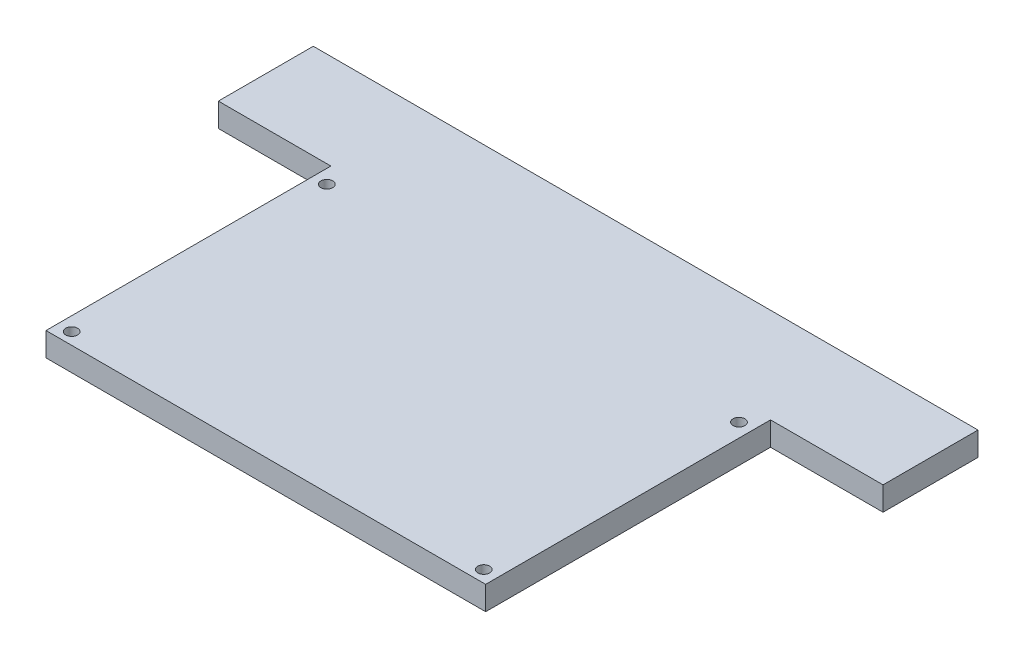
SolidWorks part; units mm, degrees
ref_plane "Front Plane" through (0, 0, 0) normal (0, 0, 1) x (1, 0, 0)
ref_plane "Top Plane" through (0, 0, 0) normal (0, 1, 0) x (1, 0, 0)
ref_plane "Right Plane" through (0, 0, 0) normal (1, 0, 0) x (0, 0, -1)
sketch "Sketch1" plane through (0, 0, 0) normal (0, 1, 0) x (1, 0, 0)
  line L0 (0, 0) -> (0, -50000) construction
  line L1 (-58.801, -38.1) -> (58.801, -38.1)
  line L2 (-58.801, -38.1) -> (-58.801, 38.1)
  line L3 (-58.801, 38.1) -> (58.801, 38.1)
  line L4 (58.801, -38.1) -> (58.801, 38.1)
  line L5 (-58.801, -38.1) -> (58.801, 38.1) construction
  line L6 (-58.801, 38.1) -> (58.801, -38.1) construction
  line L7 (-88.9, 63.5) -> (88.9, 63.5)
  line L8 (-88.9, 63.5) -> (-88.9, 38.1)
  line L9 (-88.9, 38.1) -> (88.9, 38.1)
  line L10 (88.9, 63.5) -> (88.9, 38.1)
  line L11 (-88.9, 63.5) -> (88.9, 38.1) construction
  line L12 (-88.9, 38.1) -> (88.9, 63.5) construction
  circle A0 centre (-55.118, 33.3375) radius 1.5875
  circle A1 centre (-55.118, -34.925) radius 1.5875
  circle A2 centre (55.118, -34.925) radius 1.5875
  circle A3 centre (55.118, 33.3375) radius 1.5875
  point P0 (0, 0)
  point P6 (0, 50.8)
  point P21 (0, 86.0414)
  dimension "D4" = 3.175
  dimension "D5" = 4.7625
  dimension "D7" = 3.175
  dimension "D10" = 3.175
  dimension "D13" = 3.175
  dimension "D16" = 25.4
  dimension "D1" = 76.2
  dimension "D2" = 117.602
  dimension "D3" = 177.8
  dimension "D6" = 3.683
  dimension "D8" = 3.683
  dimension "D9" = 3.175
  dimension "D11" = 3.683
  dimension "D12" = 3.175
  dimension "D14" = 4.7625
  dimension "D15" = 3.683
extrude "Boss-Extrude2" add sketch "Sketch1" along normal blind 6.35 contours L3 | L3 | L1 L4 L3 L2 region at (0, 0, -0.0028) region at (0, 0, -50.8)
